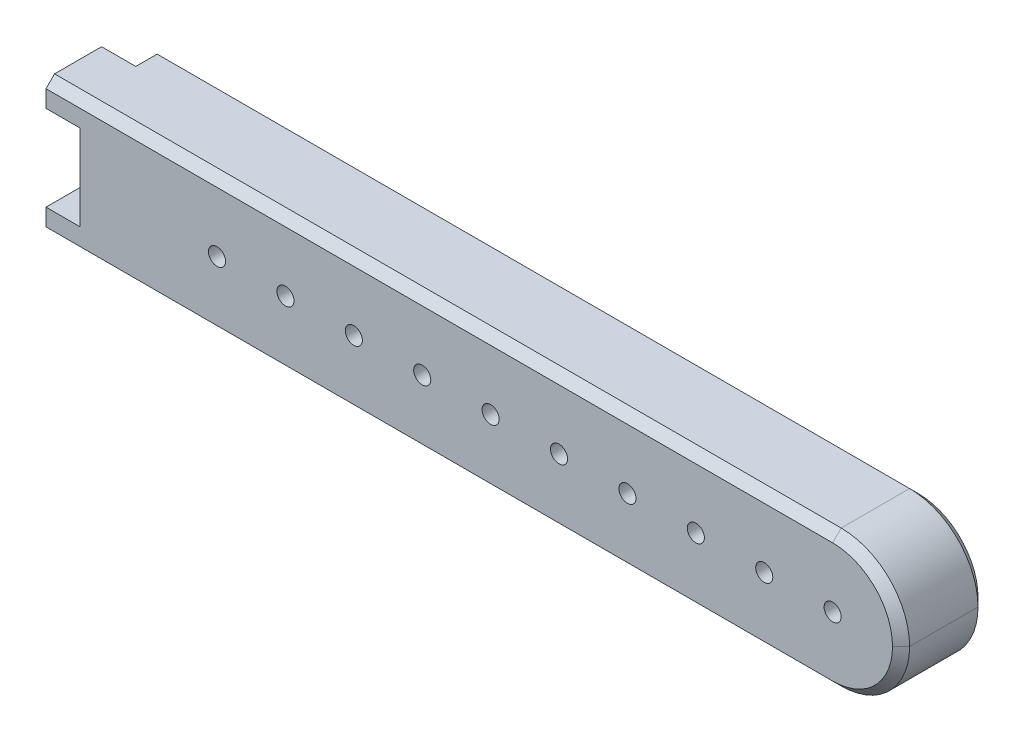
SolidWorks part; units mm, degrees
ref_plane "Front" through (0, 0, 0) normal (0, 0, 1) x (1, 0, 0)
ref_plane "Top" through (0, 0, 0) normal (0, 1, 0) x (1, 0, 0)
ref_plane "Right" through (0, 0, 0) normal (1, 0, 0) x (0, 0, -1)
sketch "Sketch1" plane through (0, 0, 0) normal (0, 0, 1) x (1, 0, 0)
  line L0 (-50, -8) -> (0, 0) construction
  line L1 (-50, 8) -> (50, 8)
  line L2 (-50, 8) -> (-50, 5)
  line L3 (-50, -8) -> (50, -8)
  line L4 (50, 8) -> (50, -8)
  line L5 (0, 0) -> (50, 8) construction
  line L6 (-50, -5) -> (-50, -8)
  line L7 (-50, 5) -> (-46, 5)
  line L9 (-50, -5) -> (-46, -5)
  line L10 (-46, 5) -> (-46, -5)
  dimension "D1" = 10
  dimension "D2" = 4
  dimension "D3" = 100
  dimension "D4" = 16
extrude "Boss-Extrude1" add sketch "Sketch1" along normal blind 10
hole_wizard "M4 Tapped Hole1" positions "3DSketch1" profile "Sketch3" tap size "M4" standard "ISO"
sketch3d "3DSketch1"
  line L0 (-46, 5, 10) -> (-46, 5, 0) construction
  line L1 (-46, 5, 0) -> (-46, -5, 0) construction
  point P0 (-46, 0, 5)
  point P7 (-46, 0, 0)
  dimension "D1" = 5
  dimension "D2" = 5
sketch "Sketch3" plane through (-46, 0, 5) normal (0, 1, 0) x (0, 0, 1)
  line L0 (0, 0) -> (0, 11.0914)
  line L1 (0, 11.0914) -> (1.65, 10.1)
  line L2 (1.65, 10.1) -> (1.65, 0.375)
  line L3 (1.65, 0.375) -> (2.025, 0)
  line L5 (2.025, 0) -> (0, 0)
  line L6 (-1.65, 0.375) -> (-2.025, 0) construction
  line L10 (0, 11.0914) -> (-1.65, 10.1) construction
  line L11 (0, -6.35) -> (0, 107.95) construction
  dimension "Tap Drill Dia." = 3.3
  dimension "Tap Drill Depth" = 10.1
  dimension "Near C'Sink Dia." = 4.05
  dimension "Near C'Sink Angle" = 90
  dimension "Drill Angle" = 118
cosmetic thread "Hole Thread1" parameters "D1"=8, "D2"=4
fillet "Fillet1" radius 8 2 edges at (50, 8, 5) (50, -8, 5)
chamfer "Chamfer1" distance 1 angle 45 8 edges at (-4, 8, 0) (47.6569, 5.6569, 0) (47.6569, -5.6569, 0) (-4, -8, 0) (-4, 8, 10) (47.6569, 5.6569, 10) (47.6569, -5.6569, 10) (-4, -8, 10)
sketch "Sketch4" plane through (0, 0, 0) normal (0, 0, -1) x (-1, 0, 0)
  line L0 (-42, 0) -> (-34, 0) construction
  line L1 (-34, 0) -> (-26, 0) construction
  line L2 (-26, 0) -> (-18, 0) construction
  line L3 (-18, 0) -> (-10, 0) construction
  line L4 (-10, 0) -> (-2, 0) construction
  line L5 (-2, 0) -> (6, 0) construction
  line L6 (6, 0) -> (14, 0) construction
  line L7 (14, 0) -> (22, 0) construction
  line L8 (22, 0) -> (30, 0) construction
  circle A0 centre (-42, 0) radius 1
  circle A1 centre (-34, 0) radius 1
  circle A2 centre (-26, 0) radius 1
  circle A3 centre (-18, 0) radius 1
  circle A4 centre (-10, 0) radius 1
  circle A5 centre (-2, 0) radius 1
  circle A6 centre (6, 0) radius 1
  circle A7 centre (14, 0) radius 1
  circle A8 centre (22, 0) radius 1
  circle A9 centre (30, 0) radius 1
  dimension "D2" = 2
  dimension "D1" = 8
extrude "Cut-Extrude1" cut sketch "Sketch4" against normal blind 10
sketch "Sketch6" plane through (-50, 0, 0) normal (-1, 0, 0) x (0, 0, 1)
  line L0 (9, -8) -> (1, -8) construction
  line L1 (3.5, -8) -> (0, -8)
  line L2 (3.5, -8) -> (3.5, 8)
  line L3 (3.5, 8) -> (0, 8)
  line L4 (0, -8) -> (0, 8)
  line L5 (9, 8) -> (1, 8) construction
  line L6 (0, 7) -> (0, 5) construction
  dimension "D1" = 3.5
extrude "Cut-Extrude3" cut sketch "Sketch6" against normal blind 4
fillet "Fillet3" radius 2 2 edges at (-48, 5, 3.5) (-48, -5, 3.5)
